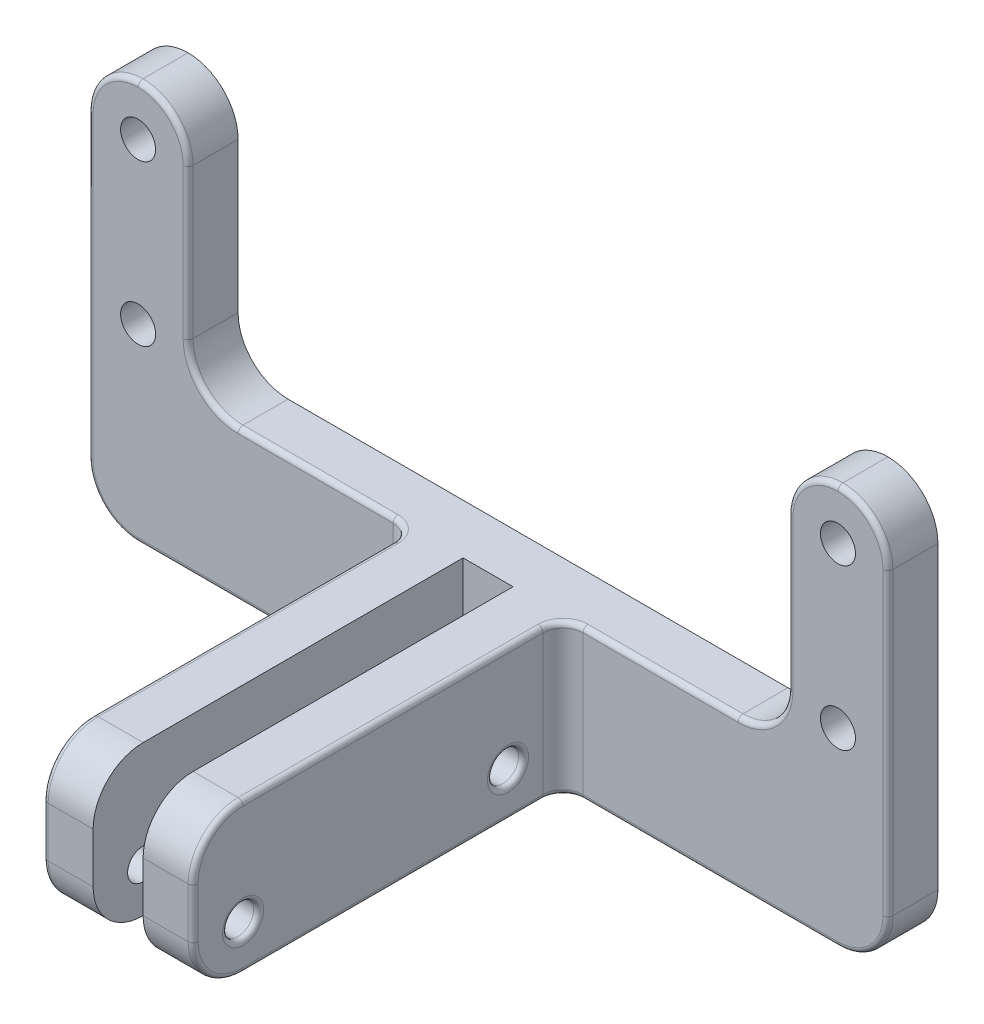
SolidWorks part; units mm, degrees
ref_plane "正面" through (0, 0, 0) normal (0, 0, 1) x (1, 0, 0)
ref_plane "平面" through (0, 0, 0) normal (0, 1, 0) x (1, 0, 0)
ref_plane "右側面" through (0, 0, 0) normal (1, 0, 0) x (0, 0, -1)
sketch "ｽｹｯﾁ1" plane through (0, 0, 0) normal (0, 0, 1) x (1, 0, 0)
  line L1 (40, 20) -> (-40, 20)
  line L2 (40, 20) -> (40, -20)
  line L3 (40, -20) -> (-40, -20)
  line L4 (-40, 20) -> (-40, -20)
  line L5 (40, 20) -> (-40, -20) construction
  line L6 (40, -20) -> (-40, 20) construction
  point P0 (0, 0)
  dimension "D1" = 80
  dimension "D2" = 40
extrude "ﾎﾞｽ - 押し出し1" add sketch "ｽｹｯﾁ1" along normal blind 5
sketch "ｽｹｯﾁ2" plane through (0, 0, 0) normal (0, 0, 1) x (1, 0, 0)
  line L0 (40, -20) -> (40, 20) construction
  line L1 (40, 20) -> (-40, 20) construction
  line L2 (0, 20) -> (0, -20) construction
  line L3 (-40, -20) -> (40, -20) construction
  circle A0 centre (35, 15) radius 1.75
  circle A1 centre (35, -1) radius 1.75
  circle A2 centre (-35, 15) radius 1.75
  circle A3 centre (-35, -1) radius 1.75
  dimension "D1" = 3.5
  dimension "D2" = 3.5
  dimension "D3" = 5
  dimension "D4" = 5
  dimension "D5" = 0
  dimension "D6" = 16
extrude "ｶｯﾄ - 押し出し1" cut sketch "ｽｹｯﾁ2" along normal through all
sketch "ｽｹｯﾁ3" plane through (0, 0, 5) normal (0, 0, 1) x (1, 0, 0)
  line L0 (0, 20) -> (0, -20) construction
  line L1 (40, 20) -> (-40, 20) construction
  line L2 (-40, -20) -> (40, -20) construction
  line L3 (7.5, -20) -> (7.5, -5)
  line L4 (-2.5, -20) -> (-7.5, -20)
  line L5 (-2.5, -20) -> (-2.5, -5)
  line L6 (-2.5, -5) -> (-7.5, -5)
  line L7 (-7.5, -20) -> (-7.5, -5)
  line L8 (2.5, -5) -> (7.5, -5)
  line L9 (2.5, -20) -> (2.5, -5)
  line L10 (2.5, -20) -> (7.5, -20)
  dimension "D1" = 2.5
  dimension "D2" = 15
  dimension "D3" = 5
extrude "ﾎﾞｽ - 押し出し2" add sketch "ｽｹｯﾁ3" along normal blind 37
sketch "ｽｹｯﾁ4" plane through (-7.5, 0, 0) normal (-1, 0, 0) x (0, 0, 1)
  line L0 (42, -20) -> (5, -20) construction
  line L1 (5, -5) -> (5, -20) construction
  circle A0 centre (10.5, -15.5) radius 1.55
  circle A1 centre (37, -15.5) radius 1.55
  dimension "D1" = 3.1
  dimension "D2" = 5.5
  dimension "D3" = 3.1
  dimension "D4" = 26.5
  dimension "D5" = 4.5
extrude "ｶｯﾄ - 押し出し2" cut sketch "ｽｹｯﾁ4" against normal through all
sketch "ｽｹｯﾁ5" plane through (0, 0, 0) normal (0, 0, 1) x (1, 0, 0)
  line L0 (40, 20) -> (-40, 20) construction
  line L1 (30, 20) -> (-30, 20)
  line L2 (30, 20) -> (30, -5)
  line L3 (30, -5) -> (-30, -5)
  line L4 (-30, 20) -> (-30, -5)
  line L5 (40, -20) -> (40, 20) construction
  line L6 (-40, 20) -> (-40, -20) construction
  dimension "D1" = 25
  dimension "D2" = 10
  dimension "D3" = 10
extrude "ｶｯﾄ - 押し出し3" cut sketch "ｽｹｯﾁ5" along normal blind 5
fillet "ﾌｨﾚｯﾄ1" radius 5 4 edges at (5, -5, 42) (-5, -5, 42) (5, -20, 42) (-5, -20, 42)
fillet "ﾌｨﾚｯﾄ2" radius 5 8 edges at (-30, -5, 2.5) (30, -5, 2.5) (30, 20, 2.5) (40, 20, 2.5) (40, -20, 2.5) (-40, -20, 2.5) (-30, 20, 2.5) (-40, 20, 2.5)
fillet "ﾌｨﾚｯﾄ3" radius 2 2 edges at (7.5, -12.5, 5)
fillet "ﾌｨﾚｯﾄ4" radius 0.5 34 edges at (8.0858, -5, 5.5858) (17.25, -5, 5) (28.5355, -3.5355, 5) (30, 7.5, 5) (31.4645, 18.5355, 5) (38.5355, 18.5355, 5) (40, 0, 5) (38.5355, -18.5355, 5) (8.0858, -20, 5.5858) (-8.0858, -20, 5.5858) (-38.5355, -18.5355, 5) (-40, 0, 5) (-38.5355, 18.5355, 5) (-31.4645, 18.5355, 5) (-30, 7.5, 5) (-28.5355, -3.5355, 5) (-17.25, -5, 5) (-8.0858, -5, 5.5858) (7.5, -18.5355, 40.5355) (7.5, -12.5, 42) (7.5, -6.4645, 40.5355) (7.5, -5, 22) (7.5, -20, 22) (7.5, -17.05, 10.5) (7.5, -17.05, 37) (-7.5, -6.4645, 40.5355) (-7.5, -12.5, 42) (-7.5, -18.5355, 40.5355) (-7.5, -5, 22) (-7.5, -15.5, 12.05) (-7.5, -15.5, 38.55)
